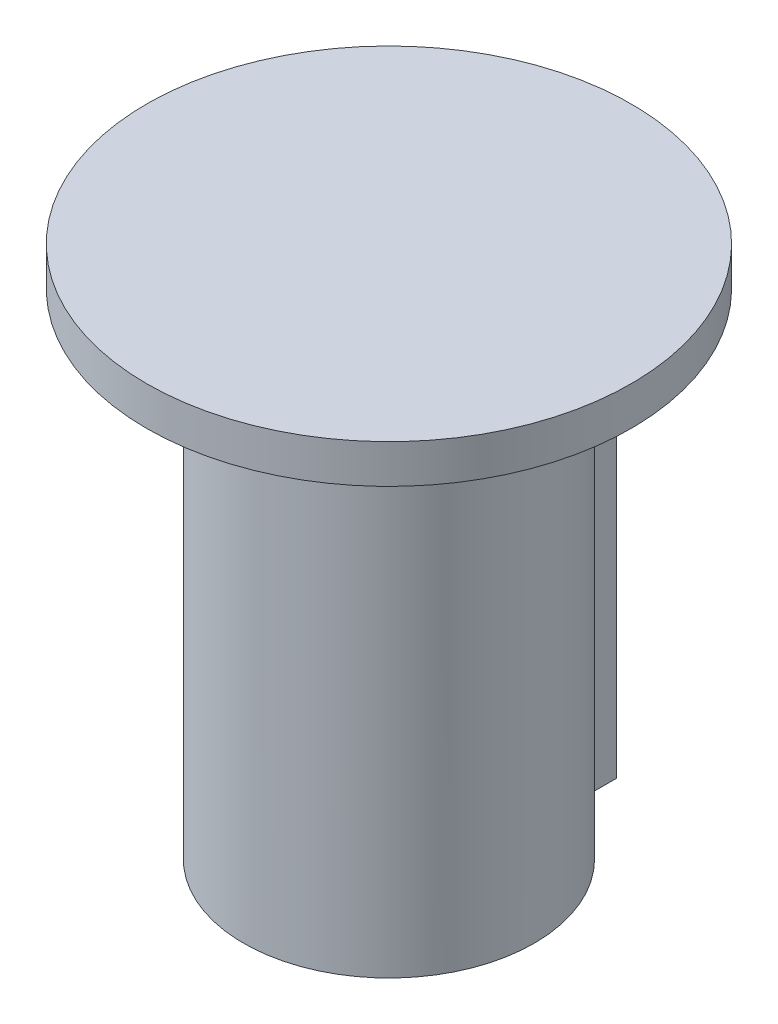
SolidWorks part; units mm, degrees
ref_plane "정면" through (0, 0, 0) normal (0, 0, 1) x (1, 0, 0)
ref_plane "윗면" through (0, 0, 0) normal (0, 1, 0) x (1, 0, 0)
ref_plane "우측면" through (0, 0, 0) normal (1, 0, 0) x (0, 0, -1)
sketch "스케치1" plane through (0, 0, 0) normal (0, 1, 0) x (1, 0, 0)
  line L0 (-0.9, 2.8618) -> (-0.9, 3.8)
  line L1 (-0.9, 3.8) -> (0.9, 3.8)
  line L2 (0.9, 3.8) -> (0.9, 2.8618)
  circle A0 centre (0, 0) radius 3
  dimension "D1" = 6
  dimension "D2" = 3.8
  dimension "D3" = 0.9
  dimension "D4" = 1.8
extrude "보스-돌출2" add sketch "스케치1" along normal blind 11 contours A0 region at (0, 0, 0)
extrude "보스-돌출3" add sketch "스케치1<3>" along normal blind 6.6 contours A0 L2 L1 L0 region at (0, 0, -3.3762)
sketch "스케치1<3>" plane through (0, 0, 0) normal (0, 1, 0) x (1, 0, 0) same geometry as "스케치1"
sketch "스케치2" plane through (0, 11, 0) normal (0, 1, 0) x (1, 0, 0)
  line L5 (-1.2, 1.1495) -> (1.2, 1.1495)
  line L6 (1.2, 1.1495) -> (1.2, 2.7495)
  line L7 (-1.2, 1.1495) -> (-1.2, 2.7495)
  line L8 (0, 0) -> (0, 1.1495) construction
  line L9 (-1.2, 2.7495) -> (0, 4.828)
  line L10 (0, 4.828) -> (1.2, 2.7495)
  circle A0 centre (0, 0) radius 3 construction
  dimension "D1" = 1.6
  dimension "D5" = 2.4
  dimension "D6" = 60
  dimension "D7" = 150
sketch "스케치3" plane through (0, 11, 0) normal (0, 1, 0) x (1, 0, 0)
  circle A0 centre (0, 0) radius 5
extrude "보스-돌출4" add sketch "스케치3" against normal blind 0.8
